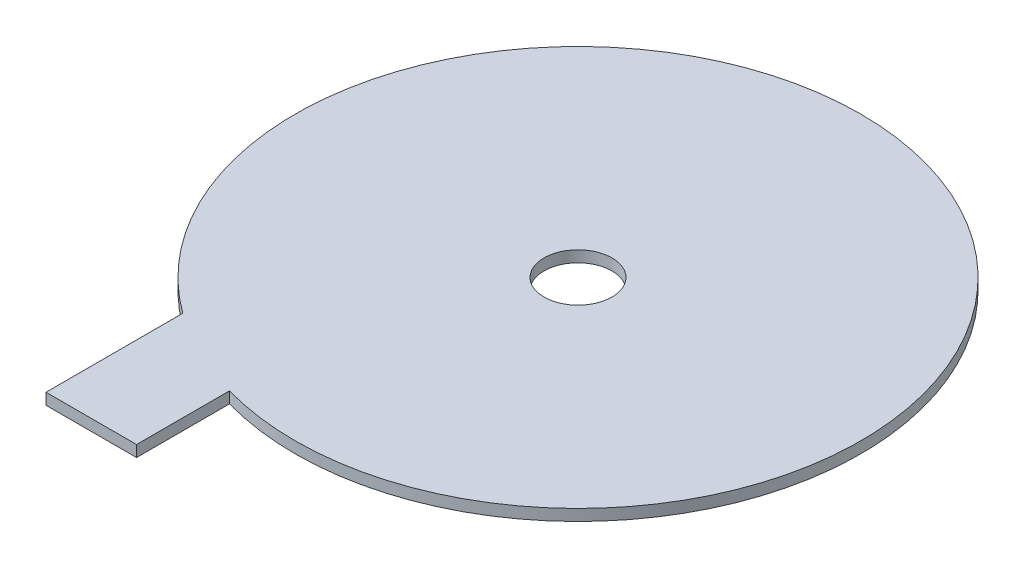
SolidWorks part; units mm, degrees
ref_plane "Front Plane" through (0, 0, 0) normal (0, 0, 1) x (1, 0, 0)
ref_plane "Top Plane" through (0, 0, 0) normal (0, 1, 0) x (1, 0, 0)
ref_plane "Right Plane" through (0, 0, 0) normal (1, 0, 0) x (0, 0, -1)
sketch "Sketch1" plane through (0, 0, 0) normal (0, 1, 0) x (1, 0, 0)
  circle A0 centre (0, 0) radius 50
extrude "Boss-Extrude1" add sketch "Sketch1" along normal blind 2
sketch "Sketch2" plane through (0, 2, 0) normal (0, 1, 0) x (1, 0, 0)
  circle A0 centre (0, 0) radius 6
extrude "Cut-Extrude1" cut sketch "Sketch2" against normal blind 2
sketch "Sketch3" plane through (0, 0, 0) normal (0, -1, 0) x (1, 0, 0)
  line L1 (-29.4445, 0) -> (-13.4445, 0)
  line L2 (-29.4445, 0) -> (-29.4445, 64.5799)
  line L3 (-29.4445, 64.5799) -> (-13.4445, 64.5799)
  line L4 (-13.4445, 0) -> (-13.4445, 64.5799)
  dimension "D1" = 16
  dimension "D2" = 13.4445
  dimension "D3" = 64.5799
extrude "Boss-Extrude2" add sketch "Sketch3" against normal through all
sketch "Sketch4" plane through (0, 2, 0) normal (0, 1, 0) x (1, 0, 0)
  line L4 (-26, -48.23) -> (-26, -61.13)
  line L5 (-20.1, -48.23) -> (-26, -48.23)
  line L6 (-20.1, -61.13) -> (-20.1, -48.23)
  line L7 (-26, -61.13) -> (-20.1, -61.13)
  line L8 (-26, -48.23) -> (-26, -61.13)
  line L9 (-20.1, -48.23) -> (-26, -48.23)
  line L10 (-20.1, -61.13) -> (-20.1, -48.23)
  line L11 (-26, -61.13) -> (-20.1, -61.13)
  dimension "D1" = 0
ref_plane "Plane1" through (20.6207, -108.6, 68.8607) normal (1, 0, 0) x (0, 0, -1)
sketch "Sketch7" plane through (0, 2, 0) normal (0, 1, 0) x (1, 0, 0)
  line L4 (-26, -48.23) -> (-26, -61.13)
  line L5 (-20.1, -48.23) -> (-26, -48.23)
  line L6 (-20.1, -61.13) -> (-20.1, -48.23)
  line L7 (-26, -61.13) -> (-20.1, -61.13)
  line L8 (-26, -48.23) -> (-26, -61.13)
  line L9 (-20.1, -48.23) -> (-26, -48.23)
  line L10 (-20.1, -61.13) -> (-20.1, -48.23)
  line L11 (-26, -61.13) -> (-20.1, -61.13)
  dimension "D1" = 0
